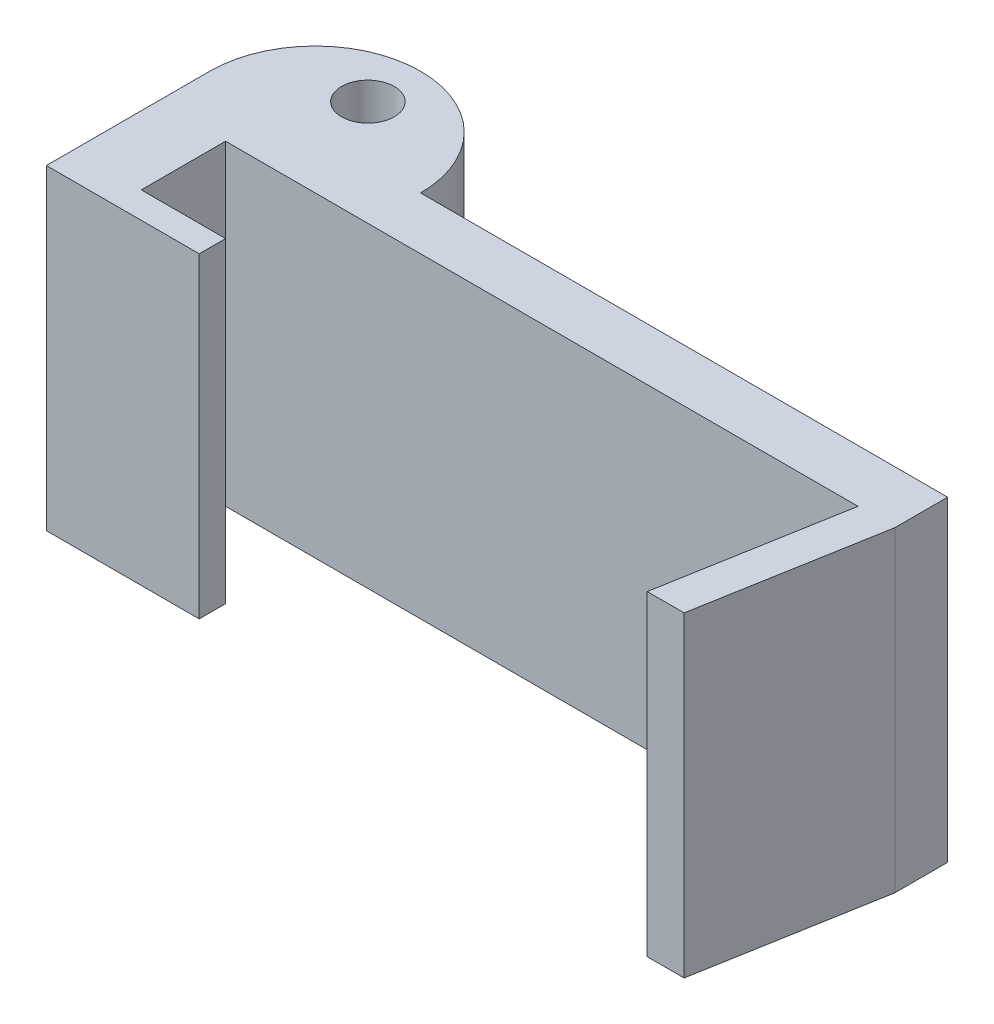
SolidWorks part; units mm, degrees
ref_plane "Front Plane" through (0, 0, 0) normal (0, 0, 1) x (1, 0, 0)
ref_plane "Top Plane" through (0, 0, 0) normal (0, 1, 0) x (1, 0, 0)
ref_plane "Right Plane" through (0, 0, 0) normal (1, 0, 0) x (0, 0, -1)
sketch "Sketch1" plane through (0, 0, 0) normal (0, 1, 0) x (1, 0, 0)
  line L1 (0, 0) -> (14, 0)
  line L2 (0, 0) -> (0, -1)
  line L3 (0, -1) -> (14, -1)
  line L4 (14, 0) -> (14, -1)
  line L5 (14, -1) -> (13.3, -1)
  line L6 (14, -1) -> (13.4005, -4.4)
  line L7 (13.4005, -4.4) -> (12.7005, -4.4)
  line L8 (13.3, -1) -> (12.7005, -4.4)
  line L9 (0, -1) -> (1.3, -1)
  line L10 (0, -1) -> (0, -3.1)
  line L11 (0, -3.1) -> (1.3, -3.1)
  line L12 (1.3, -1) -> (1.3, -3.1)
  line L13 (1.3, -3.1) -> (2.9, -3.1)
  line L14 (1.3, -3.1) -> (1.3, -2.6)
  line L15 (1.3, -2.6) -> (2.9, -2.6)
  line L16 (2.9, -3.1) -> (2.9, -2.6)
  arc A0 (0, 0) -> (4, 0) centre (2, 0) cw
  circle A1 centre (2, 1) radius 0.5
  dimension "D10" = 1
  dimension "D11" = 2
  dimension "D1" = 14
  dimension "D2" = 0.7
  dimension "D3" = 1
  dimension "D4" = 1.6
  dimension "D5" = 0.5
  dimension "D6" = 12
  dimension "D7" = 1.6
  dimension "D8" = 3.4
  dimension "D9" = 80
  dimension "D12" = 1
extrude "Boss-Extrude1" add sketch "Sketch1" along normal blind 6 contours L4 L1 L2 L3 | L12 L3 L10 L11 | L3 L8 L7 L6 | L8 | A0 L1 A1 | L14 L15 L16 L13 region at (2, 0, -1.9553) region at (7, 0, 0.5) region at (0.65, 0, 2.05) region at (13.3502, 0, 2.7)
